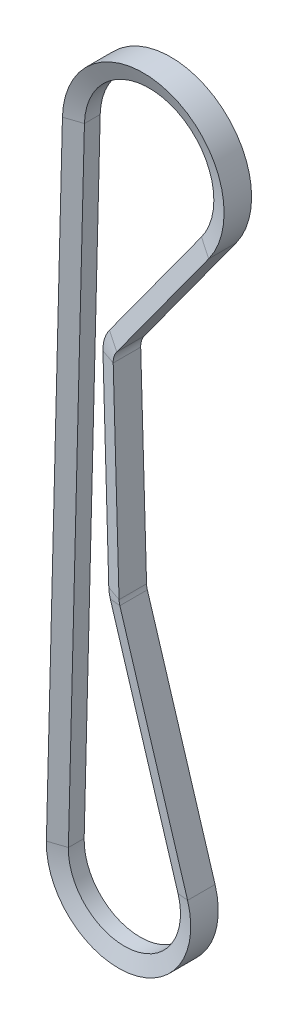
SolidWorks part; units mm, degrees
ref_plane "Front Plane" through (0, 0, 0) normal (0, 0, 1) x (1, 0, 0)
ref_plane "Top Plane" through (0, 0, 0) normal (0, 1, 0) x (1, 0, 0)
ref_plane "Right Plane" through (0, 0, 0) normal (1, 0, 0) x (0, 0, -1)
sketch "Sketch2" plane through (0, 0, 0) normal (0, 0, 1) x (1, 0, 0)
  line L0 (0, 0) -> (1, 0) construction
  line L1 (0, 0) -> (0, 1) construction
  line L12 (-24.992, 0.6314) -> (-19.4361, 220.5408)
  line L14 (31.2109, 203.3804) -> (-0.6462, 159.5135)
  line L15 (-1.8555, 155.5983) -> (0.1711, 85.6277)
  line L16 (0.4465, 83.9528) -> (23.9051, 7.3175)
  arc A4 (-19.4361, 220.5408) -> (31.2109, 203.3804) centre (8.555, 219.8336) cw
  arc A7 (23.9051, 7.3175) -> (-24.992, 0.6314) centre (0, 0) cw
  arc A8 (-0.6462, 159.5135) -> (-1.8555, 155.5983) centre (4.4918, 155.7822) ccw
  arc A9 (0.1711, 85.6277) -> (0.4465, 83.9528) centre (6.5184, 85.8115) ccw
ref_plane "Plane4" through (23.9051, 7.3175, 0) normal (0.2927, -0.9562, 0) x (-0.9562, -0.2927, 0)
sketch "Sketch3" plane through (23.9051, 7.3175, 0) normal (0.2927, -0.9562, 0) x (-0.9562, -0.2927, 0)
  line L0 (0, -4.7625) -> (0, 4.7625)
  line L1 (0, -4.7625) -> (5.588, -2.7286)
  line L2 (5.588, -2.7286) -> (5.588, 2.7286)
  line L3 (5.588, 2.7286) -> (0, 4.7625)
  line L4 (0, 0) -> (5.588, 0) construction
  dimension "D1" = 9.525
  dimension "D2" = 5.588
  dimension "D3" = 40
sweep "Sweep1" add profiles "Sketch3" path "Sketch2"
